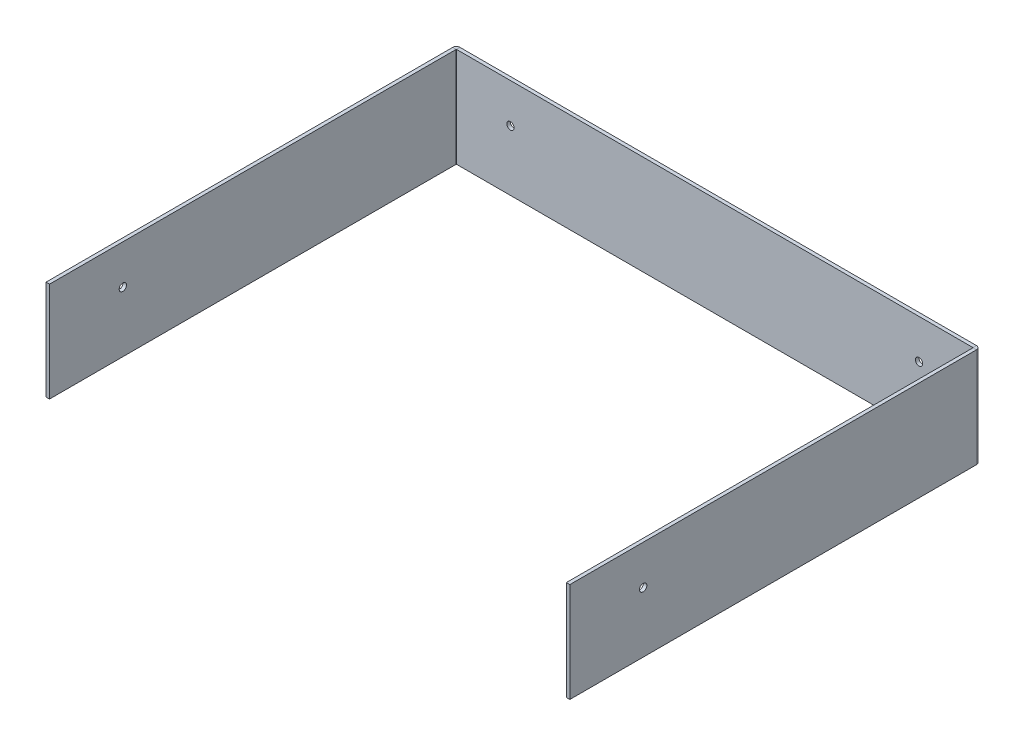
SolidWorks part; units mm, degrees
note: The reader was unsure of these and kept them because the rebuilt part matched: flange length of "Kante-Lasche1".
material "1.4301 (X5CrNi18-10)"
ref_plane "Ebene1" through (0, 0, 0) normal (0, 0, 1) x (1, 0, 0)
ref_plane "Ebene2" through (0, 0, 0) normal (0, 1, 0) x (1, 0, 0)
ref_plane "Ebene3" through (0, 0, 0) normal (1, 0, 0) x (0, 0, -1)
sketch "Skizze1" plane through (0, 0, 0) normal (0, 0, 1) x (1, 0, 0)
  line L0 (0, 28.5) -> (0, 0) construction
  line L1 (-150, 28.5) -> (150, 28.5)
  line L2 (-150, 28.5) -> (-150, -28.5)
  line L3 (-150, -28.5) -> (150, -28.5)
  line L4 (150, 28.5) -> (150, -28.5)
  line L5 (0, 0) -> (150, 0) construction
  circle A0 centre (-117, 6) radius 2.1
  circle A1 centre (117, 6) radius 2.1
  dimension "D3" = 22.5
  dimension "D4" = 33
  dimension "D5" = 4.2
  dimension "D1" = 300
  dimension "D2" = 57
sheet metal parameters "Blech1" thickness 2 parameters "D1"=0.1
base flange "Basis-Blech1" sketch "Skizze1" thickness 2 reverse thickness direction no parameters "D1"=0.1
edge flange "Kante-Lasche1" sketch "Skizze8" flange profiles "Skizze8", "Skizze9" flange angle 90 flange length 235 flange position material inside bend radius 0.1 thickness 2 relief rectangular parameters "D6"=10, "D8"=1
sketch "Skizze8" plane through (-150, 0, 0) normal (-1, 0, 0) x (0, -1, 0)
  line L2 (-28.5, 0) -> (-28.5, 233)
  line L3 (-28.5, 233) -> (28.5, 233)
  line L4 (28.5, 233) -> (28.5, 0)
  line L7 (-28.5, 0) -> (28.5, 0) construction
  line L8 (-28.5, 0) -> (28.5, 0)
sketch "Skizze9" plane through (150, 0, 0) normal (1, 0, 0) x (0, 1, 0)
  line L2 (28.5, 0) -> (28.5, 233)
  line L3 (28.5, 233) -> (-28.5, 233)
  line L4 (-28.5, 233) -> (-28.5, 0)
  line L6 (-28.5, 0) -> (28.5, 0) construction
  line L7 (-28.5, 0) -> (28.5, 0)
bend "Kantenbiegung1" bend radius 0.1 bend angle 90 parameters "D5"=1
bend "Kantenbiegung2" bend radius 0.1 bend angle 90 parameters "D5"=2
sketch "Skizze10" plane through (150, 0, 0) normal (1, 0, 0) x (0, 0, -1)
  line L0 (-0.1, 28.5) -> (-233, 28.5) construction
  line L1 (2, 28.5) -> (2, -28.5) construction
  circle A0 centre (-191, 6) radius 2.1
  dimension "D1" = 4.2
  dimension "D2" = 22.5
  dimension "D3" = 193
extrude "Schnitt-Linear austragen1" cut sketch "Skizze10" against normal through all normal cut yes
flat pattern "Abwicklung1" [suppressed]
sketch "Biegung-Linien1" plane through (0, 0, -2) normal (0, 0, -1) x (-1, 0, 0)
  line L0 (-148.7639, -28.5) -> (-148.7639, 28.5) construction
  line L1 (148.7639, 28.5) -> (148.7639, -28.5) construction
  line L2 (-148.7639, -28.5) -> (-148.7639, 28.5) construction
  line L3 (148.7639, 28.5) -> (148.7639, -28.5) construction
sketch3d "Rahmen1" [suppressed]
  line L0 (232.5279, 0, 0) -> (-532.5279, 0, 0) construction
  line L1 (232.5279, 57, 0) -> (-532.5279, 57, 0) construction
  line L2 (232.5279, 0, 0) -> (232.5279, 57, 0) construction
  line L3 (-532.5279, 0, 0) -> (-532.5279, 57, 0) construction
bend of the flat pattern "Abwickeln-<Kantenbiegung1>1"
bend of the flat pattern "Abwickeln-<Kantenbiegung2>1"
